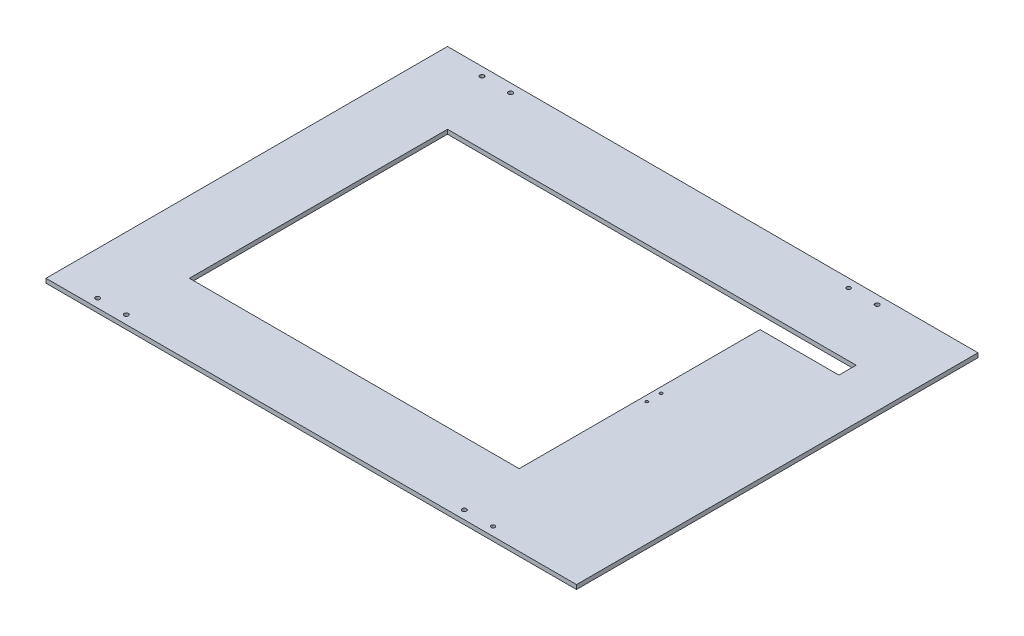
SolidWorks part; units mm, degrees
ref_plane "Front Plane" through (0, 0, 0) normal (0, 0, 1) x (1, 0, 0)
ref_plane "Top Plane" through (0, 0, 0) normal (0, 1, 0) x (1, 0, 0)
ref_plane "Right Plane" through (0, 0, 0) normal (1, 0, 0) x (0, 0, -1)
sketch "Sketch1" plane through (0, 0, 0) normal (0, 1, 0) x (1, 0, 0)
  line L1 (0, 0) -> (370, 0)
  line L2 (0, 0) -> (0, 280)
  line L3 (0, 280) -> (370, 280)
  line L4 (370, 0) -> (370, 280)
  line L5 (50, 50) -> (280, 50)
  line L6 (50, 50) -> (50, 230)
  line L7 (50, 230) -> (280, 230)
  line L8 (280, 50) -> (280, 230)
  line L9 (50, 280) -> (50, 274) construction
  line L10 (50, 274) -> (30, 274) construction
  line L12 (185, 280) -> (185, 0) construction
  line L13 (0, 140) -> (370, 140) construction
  line L14 (284, 140) -> (284, 145) construction
  line L15 (284, 140) -> (284, 135) construction
  circle A0 centre (30, 274) radius 1.5
  circle A1 centre (50, 274) radius 1.5692
  circle A2 centre (30, 6) radius 1.5
  circle A3 centre (50, 6) radius 1.5
  circle A4 centre (285.7569, 273.9854) radius 1.3573
  circle A5 centre (305.7569, 273.9346) radius 1.5
  circle A6 centre (285.7569, 6.0015) radius 1.5
  circle A7 centre (305.7569, 6.0068) radius 1.3225
  circle A8 centre (284, 145) radius 1
  circle A9 centre (284, 135) radius 1
  dimension "D11" = 3
  dimension "D12" = 2
  dimension "D1" = 370
  dimension "D2" = 280
  dimension "D3" = 230
  dimension "D4" = 50
  dimension "D5" = 50
  dimension "D6" = 50
  dimension "D8" = 6
  dimension "D10" = 20
  dimension "D13" = 4
  dimension "D14" = 10
  dimension "D15" = 20
  dimension "D16" = 20
  dimension "D17" = 20
extrude "Boss-Extrude1" add sketch "Sketch1" along normal blind 3
sketch "Sketch2" plane through (0, 3, 0) normal (0, 1, 0) x (1, 0, 0)
  line L1 (280, 230) -> (335, 230)
  line L2 (280, 230) -> (280, 218)
  line L3 (280, 218) -> (335, 218)
  line L4 (335, 230) -> (335, 218)
  dimension "D1" = 55
  dimension "D2" = 12
extrude "Cut-Extrude1" cut sketch "Sketch2" against normal blind 10
